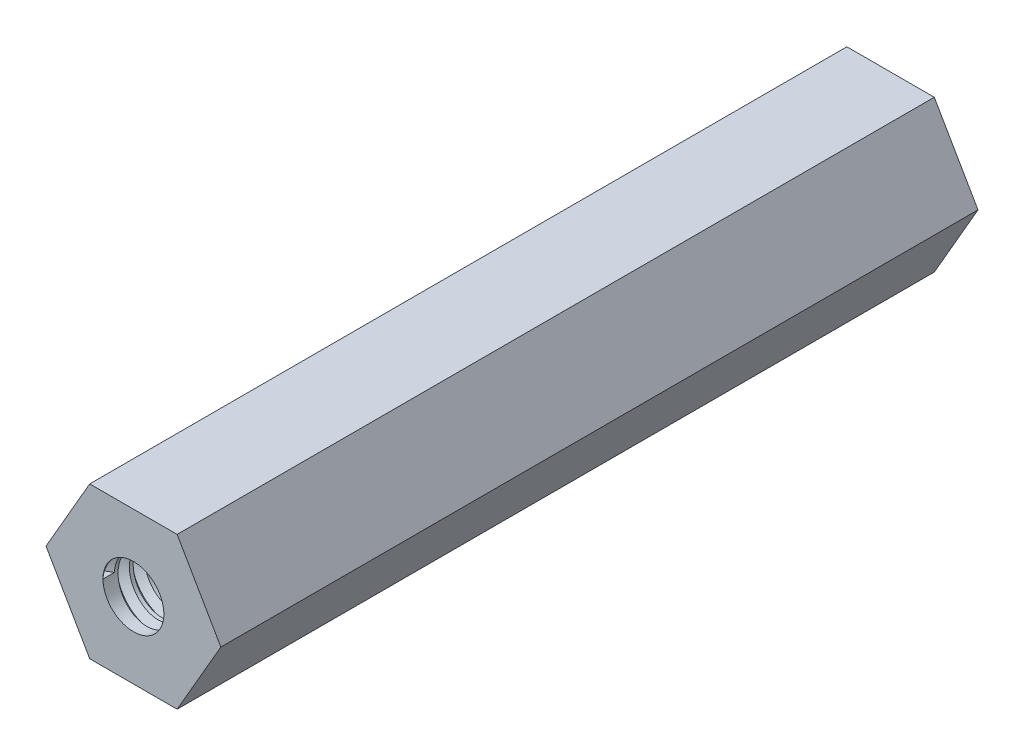
SolidWorks part; units mm, degrees
material "7075-T6 (SN)"
ref_plane "Alzado" through (0, 0, 0) normal (0, 0, 1) x (1, 0, 0)
ref_plane "Planta" through (0, 0, 0) normal (0, 1, 0) x (1, 0, 0)
ref_plane "Vista lateral" through (0, 0, 0) normal (1, 0, 0) x (0, 0, -1)
sketch "Croquis2" plane through (0, 0, 0) normal (0, 0, 1) x (1, 0, 0)
  line L1 (3.6662, -6.35) -> (7.3323, 0)
  line L2 (7.3323, 0) -> (3.6662, 6.35)
  line L3 (3.6662, 6.35) -> (-3.6662, 6.35)
  line L4 (-3.6662, 6.35) -> (-7.3323, 0)
  line L5 (-7.3323, 0) -> (-3.6662, -6.35)
  line L6 (-3.6662, -6.35) -> (3.6662, -6.35)
  circle A0 centre (0, 0) radius 6.35 construction
  dimension "D1" = 12.7
extrude "Extrusión Hex Profile" add sketch "Croquis2" along normal mid plane 63.5
sketch "Croquis3" plane through (0, 0, 0) normal (0, 0, 1) x (1, 0, 0)
  circle A0 centre (0, 0) radius 2.5527
  dimension "D1" = 5.1054
extrude "Tap Hole 1" cut sketch "Croquis3" against normal blind 19.05 from surface starting at face at (0, 0, 31.75)
extrude "Tap Hole 2" cut sketch "Croquis3<3>" along normal blind 19.05 from surface starting at face at (0, 0, -31.75)
sketch "Croquis3<3>" plane through (0, 0, 0) normal (0, 0, 1) x (1, 0, 0) same geometry as "Croquis3"
sketch "Croquis7" plane through (0, 0, 0) normal (0, 0, 1) x (1, 0, 0)
  circle A0 centre (0, 0) radius 6.8707
  dimension "D1" = 13.7414
extrude "ThunderHex" [suppressed] cut sketch "Croquis7" against normal through all both and the other way through all flip side to cut
sketch "Croquis8" plane through (0, 0, 0) normal (0, 1, 0) x (1, 0, 0)
  line L0 (0, -31.75) -> (-5.5563, -31.75) construction
  line L1 (3.6662, -31.75) -> (-3.6662, -31.75) construction
  line L3 (0, -31.75) -> (0, 0) construction
  line L4 (-5.5563, -31.75) -> (-6.35, -30.9563)
  line L5 (-6.35, -30.9563) -> (-6.35, -30.1625)
  line L6 (-6.35, -30.1625) -> (-5.9055, -30.1625)
  line L7 (-5.9055, -30.1625) -> (-5.9055, -28.575)
  line L8 (-5.9055, -28.575) -> (-12.7, -28.575)
  line L9 (-12.7, -28.575) -> (-12.7, -31.75)
  line L10 (-12.7, -31.75) -> (-5.5563, -31.75)
  line L11 (-3.6662, -31.75) -> (-7.3323, -31.75) construction
  dimension "D1" = 11.811
  dimension "D2" = 12.7
  dimension "D3" = 45
  dimension "D4" = 0.7937
  dimension "D6" = 0.7937
  dimension "D7" = 3.175
  dimension "D8" = 25.4
revolve "Retaining Ring 1" [suppressed] cut sketch "Croquis8" angle 360 about L3
sketch "Croquis9" plane through (0, 0, 0) normal (0, -1, 0) x (1, 0, 0)
  line L0 (0, -31.75) -> (-5.5563, -31.75) construction
  line L3 (0, -31.75) -> (0, 0) construction
  line L4 (-5.5563, -31.75) -> (-6.35, -30.9563)
  line L5 (-6.35, -30.9563) -> (-6.35, -30.1625)
  line L6 (-6.35, -30.1625) -> (-5.9055, -30.1625)
  line L7 (-5.9055, -30.1625) -> (-5.9055, -28.575)
  line L8 (-5.9055, -28.575) -> (-12.7, -28.575)
  line L9 (-12.7, -28.575) -> (-12.7, -31.75)
  line L10 (-12.7, -31.75) -> (-5.5563, -31.75)
  line L12 (-3.6662, -31.75) -> (3.6662, -31.75) construction
  line L13 (-7.3323, -31.75) -> (-3.6662, -31.75) construction
  dimension "D1" = 11.811
  dimension "D2" = 12.7
  dimension "D3" = 45
  dimension "D4" = 0.7937
  dimension "D6" = 0.7937
  dimension "D7" = 3.175
  dimension "D8" = 25.4
revolve "Retaining Ring 2" [suppressed] cut sketch "Croquis9" angle 360 about L3
sketch "Croquis10" plane through (0, 0, 0) normal (0, 1, 0) x (1, 0, 0)
  line L0 (0, -31.75) -> (0, 0) construction
  line L1 (3.6662, -31.75) -> (-3.6662, -31.75) construction
  line L2 (0, -31.75) -> (-5.5563, -31.75) construction
  line L3 (-3.6662, -31.75) -> (-7.3323, -31.75) construction
  line L4 (-5.5563, -31.75) -> (-6.35, -30.9563)
  line L5 (-6.35, -30.9563) -> (-6.35, -23.7998)
  line L6 (-6.35, -23.7998) -> (-9.525, -23.7998)
  line L7 (-9.525, -23.7998) -> (-9.525, -31.75)
  line L8 (-9.525, -31.75) -> (-5.5563, -31.75)
  dimension "D2" = 12.7
  dimension "D1" = 45
  dimension "D3" = 0.7937
  dimension "D4" = 7.9502
  dimension "D5" = 19.05
revolve "Round End 1" [suppressed] cut sketch "Croquis10" angle 360 about L0
sketch "Croquis12" plane through (0, 0, 0) normal (0, -1, 0) x (1, 0, 0)
  line L0 (0, -31.75) -> (0, 0) construction
  line L2 (0, -31.75) -> (-5.5562, -31.75) construction
  line L4 (-5.5562, -31.75) -> (-6.35, -30.9563)
  line L5 (-6.35, -30.9563) -> (-6.35, -23.7998)
  line L6 (-6.35, -23.7998) -> (-9.525, -23.7998)
  line L7 (-9.525, -23.7998) -> (-9.525, -31.75)
  line L8 (-9.525, -31.75) -> (-5.5562, -31.75)
  line L9 (-3.6662, -31.75) -> (3.6662, -31.75) construction
  dimension "D1" = 45
  dimension "D3" = 0.7937
  dimension "D4" = 7.9502
  dimension "D2" = 12.7
  dimension "D5" = 19.05
revolve "Round End 2" [suppressed] cut sketch "Croquis12" angle 360 about L0
thread "Rosca1" pitch 1.27 method cut profile "Perfil de rosca1" start angle 0, offset 0, length 0, pitch 1.27, diameter 5.1054
ref_plane "Plano1" through (2.5527, 0, -31.75) normal (0, -1, 0) x (1, 0, 0)
sketch "Perfil de rosca1" plane through (2.5527, 0, -31.75) normal (0, -1, 0) x (1, 0, 0)
  line L0 (0, 0) -> (0, 1.27) construction
  line L1 (0, 0) -> (0.6874, 0.3969)
  line L2 (0.6874, 0.3969) -> (0.6874, 0.5556)
  line L3 (0.6874, 0.5556) -> (0, 0.9525)
  line L4 (0.6874, 0.4762) -> (0, 0.4762) construction
  line L11 (0, 0) -> (0, 0.9525)
  point P2 (0, 0)
  dimension "Pitch" = 1.27
  dimension "Profile_Angle" = 60
  dimension "Profile_Land" = 0.1588
  dimension "Profile_Height" = 0.6874
thread "Rosca2" pitch 1.27 method cut profile "Perfil de rosca2" start angle 0, offset 0, length 0, pitch 1.27, diameter 5.1054
ref_plane "Plano2" through (-2.5527, 0, 31.75) normal (0, -1, 0) x (-1, 0, 0)
sketch "Perfil de rosca2" plane through (-2.5527, 0, 31.75) normal (0, -1, 0) x (-1, 0, 0)
  line L0 (0, 0) -> (0, 1.27) construction
  line L1 (0, 0) -> (0.6874, 0.3969)
  line L2 (0.6874, 0.3969) -> (0.6874, 0.5556)
  line L3 (0.6874, 0.5556) -> (0, 0.9525)
  line L4 (0.6874, 0.4762) -> (0, 0.4762) construction
  line L11 (0, 0) -> (0, 0.9525)
  point P2 (0, 0)
  dimension "Pitch" = 1.27
  dimension "Profile_Angle" = 60
  dimension "Profile_Land" = 0.1588
  dimension "Profile_Height" = 0.6874
equation "\"HexOD\"= 0.5pulgadas"
equation "\"Largo\"= 2.5pulgadas"
equation "\"D1@Croquis2\"=\"HexOD\""
equation "\"D1@Extrusión Hex Profile\" = \"Largo\""
equation "\"TapHole\"= IIF ( \"HexOD\" = 0.5pulgadas , 0.2010pulgadas , 0.190pulgadas )"
equation "\"D1@Croquis3\"=\"TapHole\""
equation "\"ProTapHole\"= 0.75pulgadas"
equation "\"D1@Tap Hole 1\" = \"ProTapHole\""
equation "\"D1@Tap Hole 2\" = \"ProTapHole\""
equation "\"ThunderHex\"= IIF ( \"HexOD\" = 0.5pulgadas , 0.541pulgadas , 0.4035pulgadas )"
equation "\"D1@Croquis7\"=\"ThunderHex\""
equation "\"D2@Croquis8\"=\"HexOD\""
equation "\"D1@Croquis8\"=if(\"HexOD\"=0.5pulgadas, 0.465pulgadas, 0.35pulgadas )"
equation "\"D2@Croquis9\"=\"HexOD\""
equation "\"D1@Croquis9\"=if(\"HexOD\"=0.5pulgadas, 0.465pulgadas, 0.35pulgadas )"
equation "\"D8@Croquis8\"=\"HexOD\"*2"
equation "\"D8@Croquis9\"=\"HexOD\"*2"
equation "\"D5@Croquis10\"=\"HexOD\"*1.5"
equation "\"D5@Croquis12\"=\"HexOD\"*1.5"
equation "\"D4@Croquis10\"=if( \"D2@Croquis10\"=<0.375, 0.28, 0.313)"
equation "\"D4@Croquis12\"=if( \"D2@Croquis10\"=<0.375, 0.28, 0.313)"
